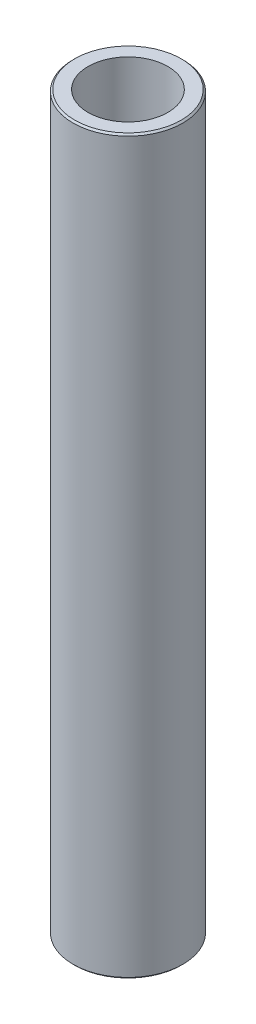
SolidWorks part; units mm, degrees
ref_plane "Front Plane" through (0, 0, 0) normal (0, 0, 1) x (1, 0, 0)
ref_plane "Top Plane" through (0, 0, 0) normal (0, 1, 0) x (1, 0, 0)
ref_plane "Right Plane" through (0, 0, 0) normal (1, 0, 0) x (0, 0, -1)
sketch "Sketch1" plane through (0, 0, 0) normal (0, 1, 0) x (1, 0, 0)
  circle A0 centre (0, 0) radius 45
  dimension "SHAFT_OD" = 90
extrude "Boss-Extrude1" add sketch "Sketch1" along normal blind 600
sketch "Sketch2" plane through (0, 0, 0) normal (0, 1, 0) x (1, 0, 0)
  circle A0 centre (0, 0) radius 32.7034
  dimension "BORE_D" = 65.4067
extrude "Cut-Extrude1" cut sketch "Sketch2" along normal through all
chamfer "Chamfer1" distance 1.3712 angle 45 2 edges at (0, 600, 45) (0, 0, 45)
